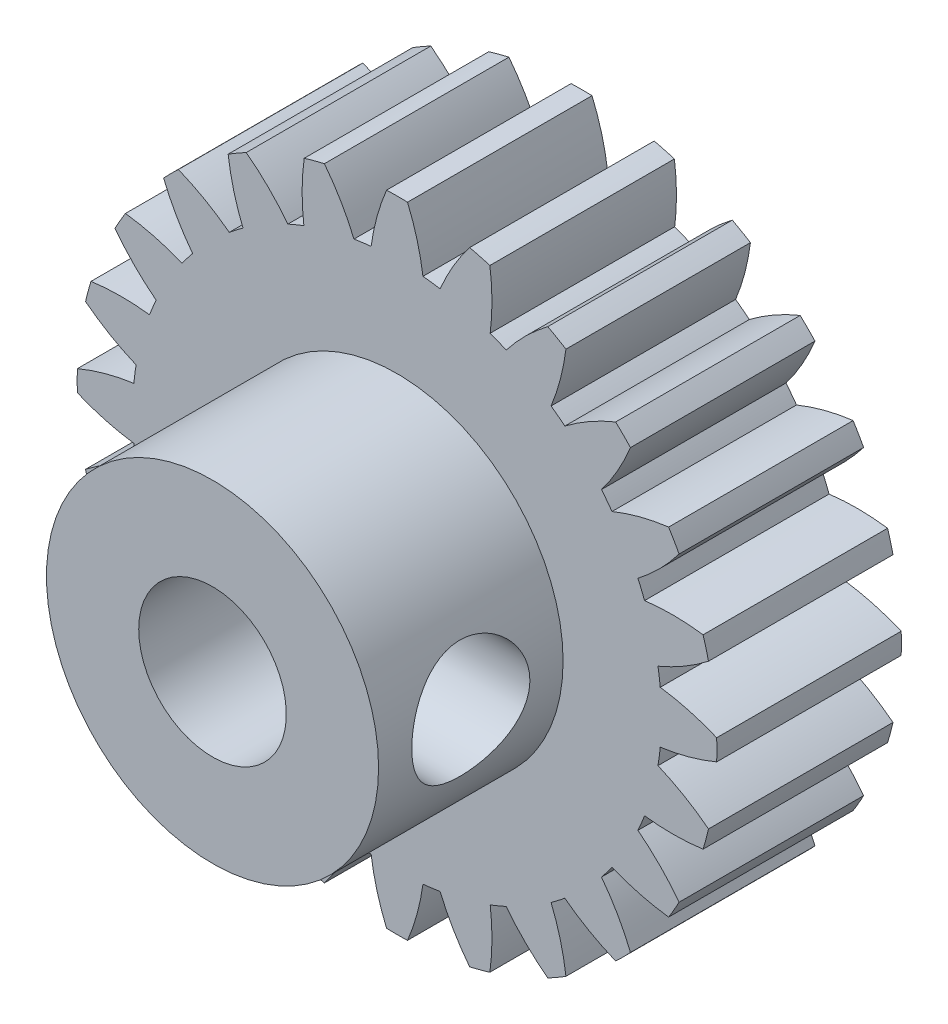
SolidWorks part; units mm, degrees
material "Alloy Steel"
ref_plane "Front Plane" through (0, 0, 0) normal (0, 0, 1) x (1, 0, 0)
ref_plane "Top Plane" through (0, 0, 0) normal (0, 1, 0) x (1, 0, 0)
ref_plane "Right Plane" through (0, 0, 0) normal (1, 0, 0) x (0, 0, -1)
sketch "Sketch1" plane through (0, 0, 0) normal (0, 1, 0) x (1, 0, 0)
  line L0 (6.8792, 0) -> (0, 0)
  line L1 (0, 0) -> (0, -3.9688)
  line L2 (0, -3.9688) -> (6.8792, -3.9688)
  line L3 (6.8792, -3.9688) -> (6.8792, 0)
  line L4 (0, 0) -> (0, -3.9688) construction
revolve "Revolve1" add sketch "Sketch1" angle 360 about L4 reverse direction yes
sketch "Sketch2" plane through (0, 0, 0) normal (0, 0, -1) x (-1, 0, 0)
  arc A0 (4.7025, 5.0209) -> (3.6327, 5.8418) centre (0, 0) ccw
  arc A1 (3.6327, 5.8418) -> (3.3134, 4.6239) centre (-1.1278, 6.4388) cw
  arc A2 (3.3134, 4.6239) -> (3.6088, 4.3973) centre (0, 0) cw
  arc A3 (3.6088, 4.3973) -> (4.7025, 5.0209) centre (6.5113, 0.5771) cw
extrude "Cut-Extrude1" cut sketch "Sketch2" against normal through all
ref_axis "Axis2" through (0, 0, 0) along (0, 0, 1)
pattern_circular "CirPattern1" count 24 over 360 about axis through (0, 0, 0) along (0, 0, 1) of "Cut-Extrude1"
sketch "Sketch26" plane through (0, 0, 0) normal (0, 1, 0) x (1, 0, 0)
  line L0 (3.5719, -3.9688) -> (0, -3.9688)
  line L1 (0, -3.9688) -> (0, -7.9375)
  line L2 (0, -7.9375) -> (3.5719, -7.9375)
  line L3 (3.5719, -7.9375) -> (3.5719, -3.9688)
  line L4 (0, -3.9688) -> (0, -7.9375) construction
revolve "Revolve2" add sketch "Sketch26" angle 360 about L4 reverse direction yes
hole_wizard "Hole1" positions "Sketch28" profile "Sketch27" legacy
sketch "Sketch28" plane through (0, 0, 0) normal (0, 0, -1) x (-1, 0, 0)
  point P0 (0, 0)
sketch "Sketch27" plane through (0, 0, 0) normal (1, 0, 0) x (0, 1, 0)
  line L0 (0, 0) -> (0, 7.9375)
  line L1 (0, 7.9375) -> (1.5875, 7.9375)
  line L2 (1.5875, 7.9375) -> (1.5875, 0)
  line L3 (1.5875, 0) -> (0, 0)
  line L4 (0, 110) -> (0, -10) construction
  dimension "Diameter" = 3.175
  dimension "Depth" = 7.9375
ref_plane "Plane1" through (0.9525, 0, 0) normal (-1, 0, 0) x (0, 0, 1)
hole_wizard "M2 Clearance Hole1" positions "Sketch30" profile "Sketch29" hole size "M2" standard "Ansi Metric"
sketch "Sketch30" plane through (0.9525, 0, 0) normal (-1, 0, 0) x (0, 0, 1)
  point P0 (5.9531, 0)
sketch "Sketch29" plane through (0.9525, 0, 5.9531) normal (0, 1, 0) x (0, 0, 1)
  line L0 (0, 0) -> (0, 5.9267)
  line L1 (0, 5.9267) -> (1.27, 5.9267)
  line L2 (1.27, 5.9267) -> (1.27, 0)
  line L5 (1.27, 0) -> (0, 0)
  line L11 (0, -6.35) -> (0, 107.95) construction
  dimension "Thru Hole Dia." = 2.54
  dimension "Thru Hole Depth" = 5.9267
